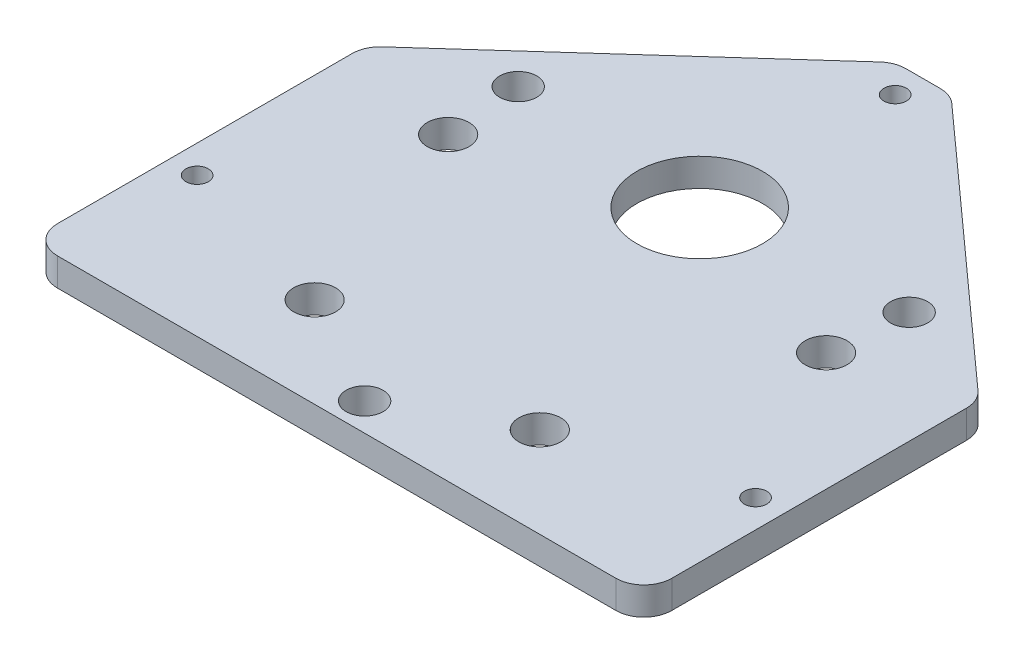
SolidWorks part; units mm, degrees
material "6061-T6 (SS)"
ref_plane "Front Plane" through (0, 0, 0) normal (0, 0, 1) x (1, 0, 0)
ref_plane "Top Plane" through (0, 0, 0) normal (0, 1, 0) x (1, 0, 0)
ref_plane "Right Plane" through (0, 0, 0) normal (1, 0, 0) x (0, 0, -1)
sketch "Sketch1" plane through (0, 0, 0) normal (0, 1, 0) x (1, 0, 0)
  line L0 (-69.85, -19.05) -> (69.85, -19.05)
  line L1 (69.85, -19.05) -> (69.85, 57.15)
  line L2 (69.85, 57.15) -> (6.35, 114.3)
  line L3 (6.35, 114.3) -> (-6.35, 114.3)
  line L4 (-6.35, 114.3) -> (-69.85, 57.15)
  line L5 (-69.85, 57.15) -> (-69.85, -19.05)
  line L6 (0, 0) -> (0, -19.05) construction
  dimension "D1" = 139.7
  dimension "D2" = 12.7
  dimension "D3" = 114.3
  dimension "D4" = 57.15
  dimension "D5" = 19.05
extrude "Boss-Extrude1" add sketch "Sketch1" along normal blind 6.35
sketch "Sketch4" plane through (0, 6.35, 0) normal (0, 1, 0) x (1, 0, 0)
  circle A0 centre (0, 63.5) radius 14.2875
  dimension "D1" = 28.575
  dimension "D2" = 63.5
extrude "Cut-Extrude2" cut sketch "Sketch4" against normal through all
extrude "Cut-Extrude3" cut sketch "Sketch5" against normal blind 50.8
sketch "Sketch5" plane through (0, 6.35, 19.05) normal (0, 1, 0) x (-0.9584, 0, 0.2853)
  circle A0 centre (21.6972, -77.741) radius 4.7625
  circle A1 centre (18.6656, -27.0315) radius 4.7625
  circle A2 centre (-30.411, -12.4209) radius 4.7625
  circle A3 centre (-60.6842, -53.2152) radius 4.7625
hole_wizard "#10 Clearance Hole1" positions "Sketch6" profile "Sketch7" hole size "#10" standard "ANSI Inch"
sketch "Sketch6" plane through (0, 6.35, 19.05) normal (0, 1, 0) x (1, 0, 0)
  point P0 (-63.5, 31.75)
  point P2 (63.5, 31.75)
  point P4 (0, 127)
sketch "Sketch7" plane through (-63.5, 6.35, -12.7) normal (1, 0, 0) x (0, 0, 1)
  line L0 (0, 0) -> (0, 52.3338)
  line L1 (0, 52.3338) -> (2.5527, 50.8)
  line L2 (2.5527, 50.8) -> (2.5527, 0)
  line L3 (2.5527, 0) -> (0, 0)
  line L4 (0, 52.3338) -> (-2.5527, 50.8) construction
  line L5 (0, -6.35) -> (0, 107.95) construction
  dimension "Hole Dia." = 5.1054
  dimension "Hole Depth" = 50.8
  dimension "Drill Angle" = 118
fillet "Fillet1" radius 6.35 6 edges at (-6.35, 3.175, -114.3) (6.35, 3.175, -114.3) (69.85, 3.175, -57.15) (69.85, 3.175, 19.05) (-69.85, 3.175, -57.15) (-69.85, 3.175, 19.05)
hole_wizard "5/16 Clearance Hole1" positions "Sketch8" profile "Sketch9" hole size "5/16" standard "ANSI Inch" end condition through all
sketch "Sketch8" plane through (0, 0, 19.05) normal (0, -1, 0) x (-1, 0, 0)
  line L0 (-44.45, 85.725) -> (0, 6.35) construction
  line L1 (0, 6.35) -> (44.45, 85.725) construction
  point P0 (-44.45, 85.725)
  point P2 (44.45, 85.725)
  point P4 (0, 6.35)
sketch "Sketch9" plane through (44.45, 0, -66.675) normal (1, 0, 0) x (0, 0, -1)
  line L0 (0, 0) -> (0, 6.35)
  line L1 (0, 6.35) -> (4.2164, 6.35)
  line L2 (4.2164, 6.35) -> (4.2164, 0)
  line L3 (4.2164, 0) -> (0, 0)
  line L4 (0, -6.35) -> (0, 107.95) construction
  dimension "Thru Hole Dia." = 8.4328
  dimension "Thru Hole Depth" = 6.35
